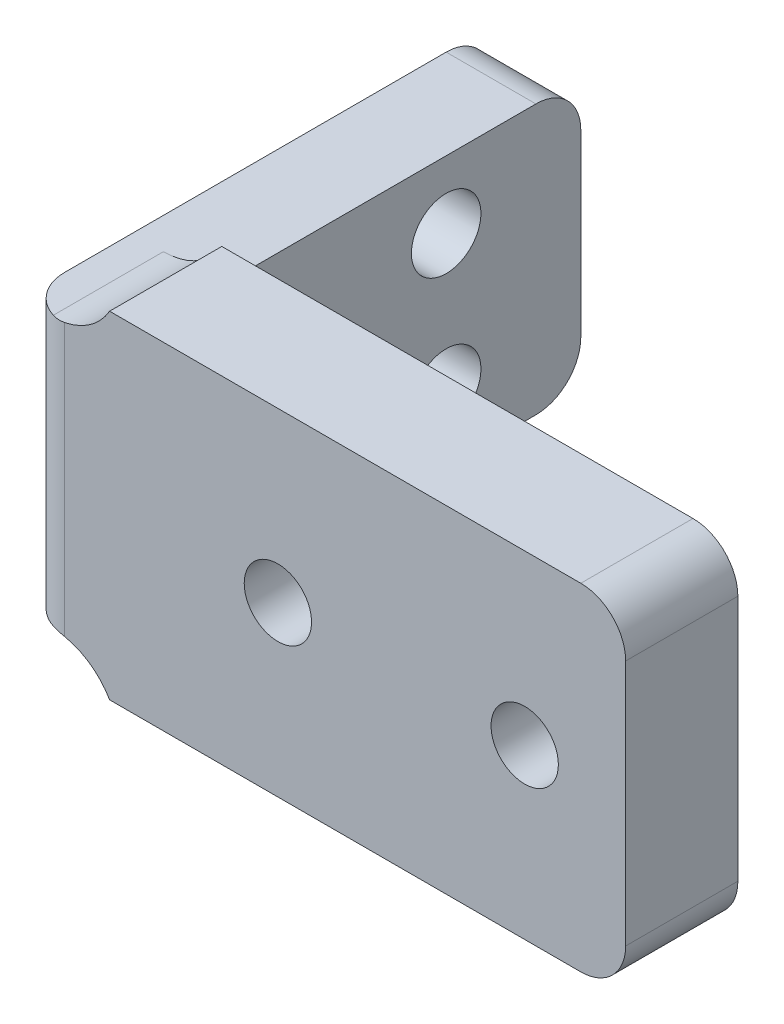
SolidWorks part; units mm, degrees
ref_plane "前视基准面" through (0, 0, 0) normal (0, 0, 1) x (1, 0, 0)
ref_plane "上视基准面" through (0, 0, 0) normal (0, 1, 0) x (1, 0, 0)
ref_plane "右视基准面" through (0, 0, 0) normal (1, 0, 0) x (0, 0, -1)
sketch "草图1" plane through (0, 0, 0) normal (0, 0, 1) x (1, 0, 0)
  line L1 (10, -7.5) -> (-10, -7.5)
  line L2 (10, -7.5) -> (10, 7.5)
  line L3 (10, 7.5) -> (-10, 7.5)
  line L4 (-10, -7.5) -> (-10, 7.5)
  line L5 (10, -7.5) -> (-10, 7.5) construction
  line L6 (10, 7.5) -> (-10, -7.5) construction
  point P0 (0, 0)
  dimension "D1" = 20
  dimension "D2" = 15
extrude "凸台-拉伸1" add sketch "草图1" along normal blind 5
sketch "草图3" plane through (0, 0, 5) normal (0, 0, 1) x (1, 0, 0)
  line L0 (0, 0) -> (5.5, 0) construction
  line L1 (0, -2.75) -> (0, 2.75) construction
  circle A0 centre (5.5, 0) radius 1.5
  circle A1 centre (-5.5, 0) radius 1.5
  dimension "D1" = 5.5
  dimension "D2" = 3
extrude "切除-拉伸2" cut sketch "草图3" against normal through all
sketch "草图4" plane through (-10, 0, 0) normal (-1, 0, 0) x (0, 0, 1)
  line L0 (2.3351, 3.221) -> (2.3351, -2.4581)
sketch "草图7" plane through (-10, 0, 0) normal (-1, 0, 0) x (0, 0, 1)
  line L4 (0, 7.5) -> (0, -7.5)
  line L5 (0, -7.5) -> (5, -7.5)
  line L6 (5, -7.5) -> (5, 7.5)
  line L7 (5, 7.5) -> (0, 7.5)
  line L8 (0, 7.5) -> (0, -7.5)
  line L9 (0, -7.5) -> (5, -7.5)
  line L10 (5, -7.5) -> (5, 7.5)
  line L11 (5, 7.5) -> (0, 7.5)
  dimension "D1" = 0
extrude "凸台-拉伸4" add sketch "草图7" along normal blind 3
sketch "草图8" plane through (-13, 0, 0) normal (-1, 0, 0) x (0, 0, 1)
  line L0 (5, -7.5) -> (5, 7.5) construction
  line L1 (5, -6) -> (-16, -6)
  line L2 (5, -6) -> (5, 6)
  line L3 (5, 6) -> (-16, 6)
  line L4 (-16, -6) -> (-16, 6)
  line L5 (5, -6) -> (-16, 6) construction
  line L6 (5, 6) -> (-16, -6) construction
  line L9 (0, 0) -> (5, 0) construction
  point P0 (-5.5, 0)
  dimension "D1" = 12
  dimension "D3" = 21
extrude "凸台-拉伸5" add sketch "草图8" along normal blind 4
sketch "草图9" plane through (-13, 0, 0) normal (1, 0, 0) x (0, 0, -1)
  line L0 (16, 0) -> (10, 0) construction
  line L1 (16, 6) -> (16, -6) construction
  line L2 (10, 0) -> (10, -3) construction
  circle A0 centre (10, -3) radius 1.55
  circle A1 centre (10, 3) radius 1.55
  dimension "D3" = 3.1
  dimension "D1" = 6
  dimension "D2" = 3
extrude "切除-拉伸3" cut sketch "草图9" against normal blind 15
fillet "圆角1" radius 3 2 edges at (-13, 6, 2.5) (-13, -6, 2.5)
fillet "圆角2" radius 2 2 edges at (10, -7.5, 2.5) (10, 7.5, 2.5)
fillet "圆角3" radius 2 3 edges at (-15, -6, -16) (-15, 6, -16) (-17, 0, 5)
